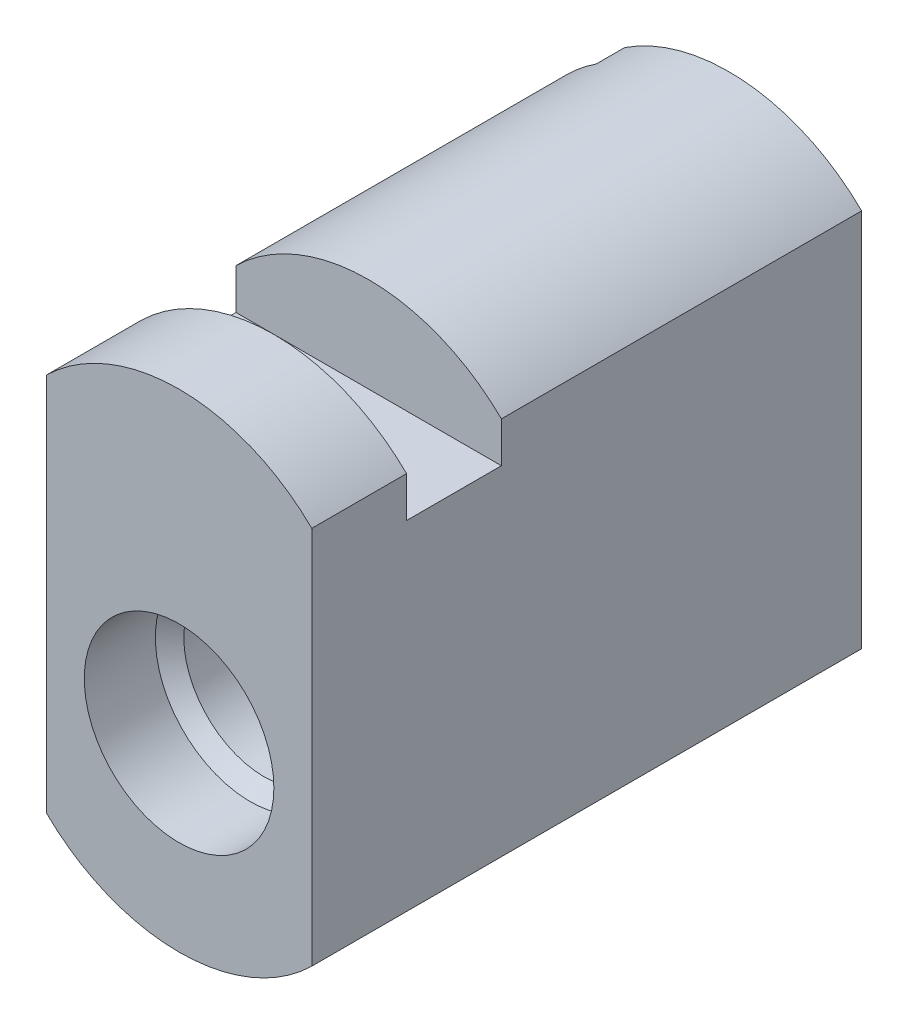
SolidWorks part; units mm, degrees
material "3D printed plastic"
ref_plane "Front Plane" through (0, 0, 0) normal (0, 0, 1) x (1, 0, 0)
ref_plane "Top Plane" through (0, 0, 0) normal (0, 1, 0) x (1, 0, 0)
ref_plane "Right Plane" through (0, 0, 0) normal (1, 0, 0) x (0, 0, -1)
sketch "Sketch1" plane through (0, 0, 0) normal (0, 0, 1) x (1, 0, 0)
  line L0 (-14, 20) -> (-14, -20)
  line L1 (-14, -20) -> (14, -20) construction
  line L2 (14, -20) -> (14, 20)
  line L3 (14, 20) -> (-14, 20) construction
  line L4 (-14, 20) -> (14, -20) construction
  arc A0 (-14, 20) -> (14, 20) centre (0, 5.7171) cw
  arc A1 (-14, -20) -> (14, -20) centre (0, -5.7171) ccw
  circle A2 centre (0, -5.7171) radius 8.5
  dimension "D2" = 17
  dimension "D3" = 20
  dimension "D1" = 28
  dimension "D4" = 40
extrude "Boss-Extrude1" add sketch "Sketch1" along normal blind 58
sketch "Sketch2" plane through (14, 0, 0) normal (1, 0, 0) x (0, 0, -1)
  line L0 (0, 25.7171) -> (-58, 25.7171) construction
  line L1 (-48, 25.7171) -> (-38, 25.7171)
  line L2 (-48, 25.7171) -> (-48, 15.7171)
  line L3 (-48, 15.7171) -> (-38, 15.7171)
  line L4 (-38, 25.7171) -> (-38, 15.7171)
  line L5 (-58, 25.7171) -> (-58, 20) construction
  dimension "D1" = 10
  dimension "D2" = 10
  dimension "D3" = 10
extrude "Cut-Extrude1" cut sketch "Sketch2" against normal through all
sketch "Sketch3" plane through (0, 0, 0) normal (0, 0, -1) x (-1, 0, 0)
  line L0 (14, 20) -> (14, -20) construction
  line L1 (11, 28.1009) -> (14, 28.1009)
  line L2 (11, 28.1009) -> (11, -28.9406)
  line L3 (11, -28.9406) -> (14, -28.9406)
  line L4 (14, 28.1009) -> (14, -28.9406)
  dimension "D1" = 3
extrude "Cut-Extrude2" cut sketch "Sketch3" against normal blind 3
sketch "Sketch4" plane through (0, 0, 58) normal (0, 0, 1) x (1, 0, 0)
  circle A0 centre (0, -5.7171) radius 10
  dimension "D1" = 20
extrude "Cut-Extrude3" cut sketch "Sketch4" against normal blind 5
chamfer "Chamfer1" distance 4 angle 45 1 edges at (8.5, -5.7171, 53)
sketch "Sketch5" plane through (0, 0, 0) normal (0, 0, -1) x (-1, 0, 0)
  circle A0 centre (0, -5.7171) radius 12.75
  dimension "D1" = 25.5
extrude "Cut-Extrude4" cut sketch "Sketch5" against normal blind 3
chamfer "Chamfer2" distance 2 angle 70 1 edges at (-8.5, -5.7171, 3) first distance on face at (-8.0611, -1.9057, 3)
sketch "Sketch6" plane through (0, 0, 0) normal (0, 0, -1) x (-1, 0, 0)
  line L0 (0, 21.2829) -> (0, -21.7171) construction
  circle A0 centre (0, -21.7171) radius 1.25
  circle A1 centre (0, 21.2829) radius 1.25
  circle A2 centre (0, -5.7171) radius 8.5 construction
  dimension "D2" = 2.5
  dimension "D3" = 16
  dimension "D1" = 43
extrude "Cut-Extrude5" cut sketch "Sketch6" against normal blind 15
